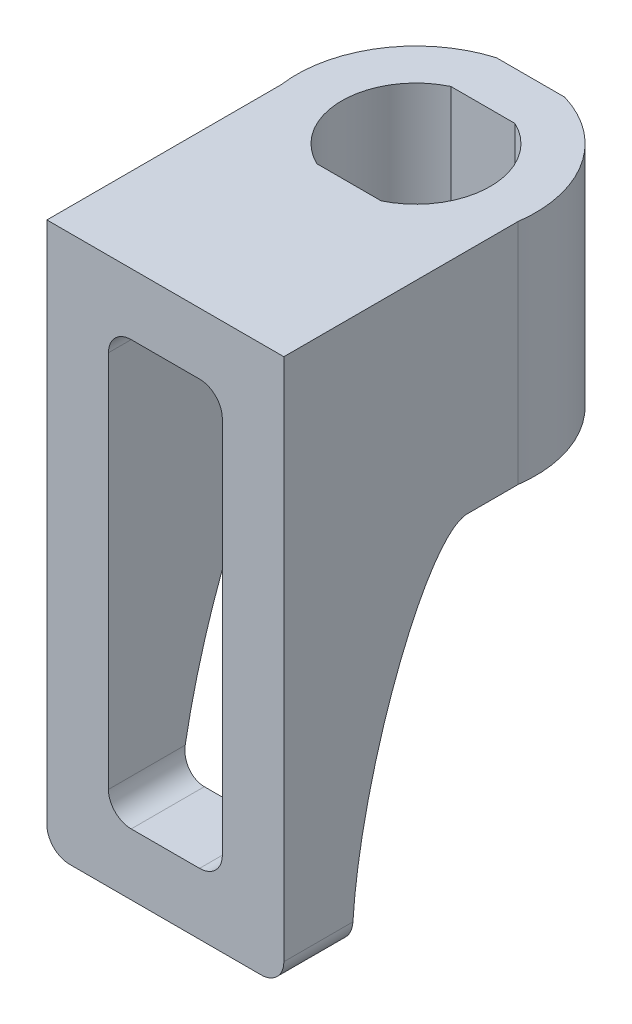
SolidWorks part; units mm, degrees
ref_plane "Front Plane" through (0, 0, 0) normal (0, 0, 1) x (1, 0, 0)
ref_plane "Top Plane" through (0, 0, 0) normal (0, 1, 0) x (1, 0, 0)
ref_plane "Right Plane" through (0, 0, 0) normal (1, 0, 0) x (0, 0, -1)
sketch "Sketch2" plane through (0, 0, 0) normal (0, 1, 0) x (1, 0, 0)
  circle A0 centre (0, 0) radius 2.625
  circle A1 centre (0, 0) radius 1.63
  dimension "D1" = 5.25
  dimension "D2" = 3.26
extrude "Boss-Extrude1" add sketch "Sketch2" along normal blind 5
sketch "Sketch3" plane through (0, 0, 0) normal (1, 0, 0) x (0, 0, -1)
  line L0 (-2.625, 0) -> (-3.187, 0.4215)
  line L1 (2.8875, 0) -> (-2.8875, 0) construction
  line L3 (-2.625, 5) -> (-2.625, 0) construction
  line L4 (-2.625, 5) -> (-2.625, 0)
  line L5 (-3.187, 0.4215) -> (-4, 0.4215)
  line L6 (-4, 0.4215) -> (-4, -7)
  line L7 (-4, -7) -> (-5.5, -7)
  line L8 (-5.5, -7) -> (-5.5, 5)
  line L9 (-5.5, 5) -> (-2.625, 5)
  line L13 (2.625, 5) -> (-2.625, 5) construction
  dimension "D1" = 2.875
  dimension "D2" = 1.5
  dimension "D4" = 12
extrude "Boss-Extrude2" add sketch "Sketch3" along normal mid plane 5.2 separate body contours L4 L0 L5 L6 L7 L8 L9
sketch "Sketch4" plane through (0, 0, 0) normal (0, -1, 0) x (1, 0, 0)
  line L0 (-2.6, 2.625) -> (-2.6, 0.3614)
  line L1 (-2.6, 0.3614) -> (0, 1.9398)
  line L2 (0, -1.5125) -> (0, 1.5125) construction
  line L3 (0, 1.9398) -> (2.6, 0.3614)
  line L4 (2.6, 0.3614) -> (2.6, 2.625)
  line L5 (-2.6, 2.625) -> (2.6, 2.625)
  circle A0 centre (0, 0) radius 2.625 construction
extrude "Boss-Extrude3" add sketch "Sketch4" against normal up to surface (5 mm away) up to face at (0, 5, 4.0625)
sketch "Sketch8" plane through (0, 5, 0) normal (0, 1, 0) x (1, 0, 0)
  line L0 (-0.7483, 1.3) -> (0.7483, 1.3) construction
  line L1 (-0.7483, -1.3) -> (0.7483, -1.3) construction
  line L2 (-0.7483, -1.3) -> (-0.7483, 1.3) construction
  line L3 (0.7483, -1.3) -> (0.7483, 1.3) construction
  line L4 (-0.7043, 1.47) -> (0.7043, 1.47)
  line L5 (0.7043, -1.47) -> (-0.7043, -1.47)
  line L6 (0.7102, 2.5271) -> (-0.7102, 2.5271)
  circle A0 centre (0, 0) radius 1.5 construction
  circle A1 centre (0, 0) radius 1.63 construction
  arc A2 (-0.7043, -1.47) -> (0.7043, -1.47) centre (0, 0) ccw
  arc A3 (-0.7043, 1.47) -> (0.7043, 1.47) centre (0, 0) cw
  circle A4 centre (0, 0) radius 2.625 construction
  arc A5 (0.7102, 2.5271) -> (-0.7102, 2.5271) centre (0, 0) ccw
  dimension "D1" = 3
  dimension "D2" = 2.6
  dimension "D3" = 0.17
  dimension "D4" = 0.17
extrude "Boss-Extrude5" add sketch "Sketch8" against normal up to surface (5 mm away) up to face at (0, 0, 0.7466)
sketch "Sketch5" plane through (0, 5, 0) normal (0, 1, 0) x (1, 0, 0)
  line L0 (0, 1.5814) -> (0, 3.3584) construction
  line L1 (0, -1.5125) -> (0, 1.5125) construction
  line L2 (0, 1.5814) -> (0, 4.2852) construction
  line L3 (0.4, 1.9876) -> (-0.4, 1.9876)
  line L4 (0.4, 1.9876) -> (0.4, 0.6814)
  line L5 (0.4, 0.6814) -> (-0.4, 0.6814)
  line L6 (-0.4, 1.9876) -> (-0.4, 0.6814)
  circle A0 centre (0, 0) radius 1.6 construction
  point P5 (0, 1.5814)
  dimension "D3" = 3.2
  dimension "D1" = 0.9
  dimension "D2" = 0.8
sketch "Sketch9" plane through (0, 5, 0) normal (0, 1, 0) x (1, 0, 0)
  line L0 (-0.75, 2.5156) -> (0.75, 2.5156)
  circle A0 centre (0, 0) radius 2.625 construction
  arc A1 (-0.75, 2.5156) -> (0.75, 2.5156) centre (0, 0) cw
  dimension "D1" = 1.5
extrude "Cut-Extrude1" cut sketch "Sketch9" against normal blind 10
sketch "Sketch15" plane through (0, 0, 5.5) normal (0, 0, 1) x (1, 0, 0)
  line L0 (2.6, -7) -> (2.6, -9.08)
  line L1 (2.6, -9.08) -> (-2.6, -9.08)
  line L2 (-2.6, -9.08) -> (-2.6, -7)
  line L3 (2.6, -7) -> (-2.6, -7)
  dimension "D1" = 2.08
hole_wizard "Ø1.0mm Dowel Hole1" positions "Sketch6" profile "Sketch7" hole size "Ø1.0" standard "ANSI Metric" end condition through all
sketch "Sketch6" plane through (0, 0, 5.5) normal (0, 0, 1) x (1, 0, 0)
  line L0 (0, -4.4086) -> (0, 4.4086) construction
  point P0 (0, 2.4197)
sketch "Sketch7" plane through (0, 2.4197, 5.5) normal (1, 0, 0) x (0, -1, 0)
  line L0 (0, 0) -> (0, 8.0156)
  line L1 (0, 8.0156) -> (0.475, 8.0156)
  line L2 (0.475, 8.0156) -> (0.475, 0)
  line L5 (0.475, 0) -> (0, 0)
  line L11 (0, -6.35) -> (0, 107.95) construction
  dimension "Thru Hole Dia." = 0.95
  dimension "Thru Hole Depth" = 8.0156
sketch "Sketch16" plane through (2.6, 0, 0) normal (1, 0, 0) x (0, 0, -1)
  line L0 (2.8875, 0) -> (-2.8875, 0) construction
  line L2 (-4, 0.4215) -> (-4, -7) construction
  line L3 (-4, -7) -> (-4, 0.6439)
  line L4 (-4, -7.5151) -> (-4, -2.4789) construction
  line L7 (-4, 0.6439) -> (-1.47, 0.6439)
  line L8 (-1.47, 0.6439) -> (-1.47, 0)
  line L9 (-2.8442, 0) -> (-0.5511, 0) construction
  spline S0 degree 3 poles (-1.47, 0) (-2.4513, 0) (-4, -4.3193) (-4, -7) knots 0 0 0 0 1 1 1 1
extrude "Boss-Extrude7" add sketch "Sketch16" against normal up to surface (5.2 mm away)
sketch "Sketch17" plane through (0, 0, 5.5) normal (0, 0, 1) x (1, 0, 0)
  line L21 (2.6, -7) -> (-2.6, -7) construction
  line L22 (-2.6, -7) -> (-2.6, 5) construction
  line L23 (2.6, -7) -> (2.6, 5) construction
  line L24 (2.6, 5) -> (-2.6, 5) construction
  line L25 (-1.25, -5.65) -> (1.25, -5.65)
  line L26 (1.25, 3.65) -> (-1.25, 3.65)
  line L27 (1.25, -5.65) -> (1.25, 3.65)
  line L28 (-1.25, 3.65) -> (-1.25, -5.65)
  dimension "D1" = 1.35
  dimension "D2" = 1.35
  dimension "D3" = 1.35
  dimension "D4" = 1.35
extrude "Cut-Extrude2" cut sketch "Sketch17" against normal blind 3
sketch "Sketch18" plane through (0, 3.65, 0) normal (0, -1, 0) x (1, 0, 0)
  line L1 (1.25, 2.5) -> (-1.25, 2.5)
  line L2 (1.25, 2.5) -> (1.25, 3.8952)
  line L3 (1.25, 3.8952) -> (-1.25, 3.8952)
  line L4 (-1.25, 2.5) -> (-1.25, 3.8952)
sketch "Sketch20" plane through (0, 0, 0) normal (0, -1, 0) x (1, 0, 0)
  line L0 (1.25, 2.5) -> (1.25, 1.47)
  line L1 (0.7043, 1.47) -> (2.6, 1.47) construction
  line L2 (1.25, 1.47) -> (-1.25, 1.47)
  line L3 (-2.6, 1.47) -> (-0.7043, 1.47) construction
  line L4 (-1.25, 1.47) -> (-1.25, 2.5)
  line L5 (-1.25, 2.5) -> (1.25, 2.5)
extrude "Cut-Extrude5" cut sketch "Sketch20" along normal blind 3
fillet "Fillet5" radius 0.5 4 edges at (1.25, 1.825, 2.5) (-1.25, 1.825, 2.5) (-1.25, 0, 1.985) (1.25, 0, 1.985)
sketch "Sketch28" plane through (0, 0, 5.5) normal (0, 0, 1) x (1, 0, 0)
  line L2 (2.6, 5) -> (-2.6, 5)
  line L9 (2.6, 5) -> (-2.6, 5)
  line L13 (-2.6, -7) -> (2.6, -7)
  line L15 (-2.6, -7) -> (2.6, -7)
  line L17 (2.6, -7) -> (2.6, 5)
  line L18 (2.6, -7) -> (2.6, 5)
  line L19 (-2.6, 5) -> (-2.6, -7)
  line L20 (-2.6, 5) -> (-2.6, -7)
  dimension "D1" = 0
fillet "Fillet15" radius 0.5 4 edges at (-1.25, -5.65, 4.6976) (1.25, -5.65, 4.6976)
fillet "Fillet16" radius 0.5 2 edges at (-2.6, -7, 4.75) (2.6, -7, 4.75)
sketch "Sketch34" plane through (0, 0, 0) normal (1, 0, 0) x (0, 0, -1)
  line L0 (-4, -7) -> (-5.5, -7) construction
  line L1 (-5, -11) -> (-2.25, -11)
  line L2 (-5, -11) -> (-5, -2.65)
  line L3 (-5, -2.65) -> (-2.25, -2.65)
  line L4 (-2.25, -11) -> (-2.25, -2.65)
  line L5 (-3.8952, -5.65) -> (-5.5, -5.65) construction
  line L6 (-5.5, -6.5) -> (-5.5, 5) construction
  dimension "D1" = 4
  dimension "D2" = 3
  dimension "D3" = 0.5
  dimension "D4" = 1.75
